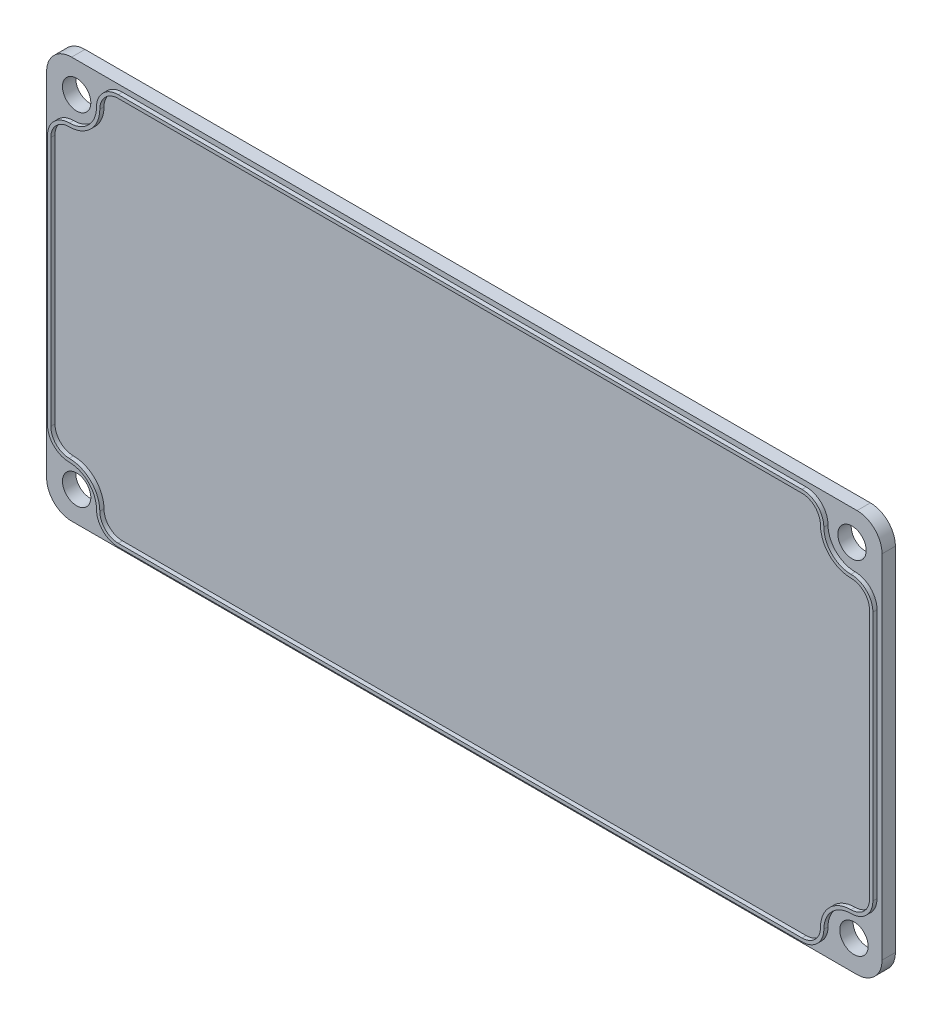
SolidWorks part; units mm, degrees
ref_plane "Plan de face" through (0, 0, 0) normal (0, 0, 1) x (1, 0, 0)
ref_plane "Plan de dessus" through (0, 0, 0) normal (0, 1, 0) x (1, 0, 0)
ref_plane "Plan de droite" through (0, 0, 0) normal (1, 0, 0) x (0, 0, -1)
sketch "Esquisse1" plane through (0, 0, 0) normal (0, 0, 1) x (1, 0, 0)
  line L0 (-50.1, -15) -> (-50.1, 21.1)
  line L1 (-47.1, 24.1) -> (47.1, 24.1)
  line L2 (50.1, 21.1) -> (50.1, -21.1)
  line L3 (47.1, -24.1) -> (-47.1, -24.1)
  line L4 (-50.1, -21.1) -> (-50.1, -15)
  arc A0 (-50.1, 21.1) -> (-47.1, 24.1) centre (-47.1, 21.1) cw
  arc A1 (47.1, 24.1) -> (50.1, 21.1) centre (47.1, 21.1) cw
  arc A2 (50.1, -21.1) -> (47.1, -24.1) centre (47.1, -21.1) cw
  arc A3 (-47.1, -24.1) -> (-50.1, -21.1) centre (-47.1, -21.1) cw
extrude "Boss.-Extru.1" add sketch "Esquisse1" along normal blind 1.6
sketch "Esquisse2" plane through (0, 0, 0) normal (0, 0, 1) x (1, 0, 0)
  line L0 (-41, 22.5) -> (41, 22.5) construction
  line L1 (48.5, 15) -> (48.5, -15) construction
  line L2 (41, -22.5) -> (-41, -22.5) construction
  line L3 (-48.5, -15) -> (-48.5, 15) construction
  line L4 (-49.7, -15) -> (-49.7, 15) construction
  line L5 (-41, 23.7) -> (41, 23.7) construction
  line L6 (49.7, 15) -> (49.7, -15) construction
  line L7 (41, -23.7) -> (-41, -23.7) construction
  line L8 (41, -23.3) -> (-41, -23.3)
  line L9 (-49.3, -15) -> (-49.3, 15)
  line L10 (-41, 23.3) -> (41, 23.3)
  line L11 (49.3, 15) -> (49.3, -15)
  arc A0 (41, 22.5) -> (42.62, 20.88) centre (41, 20.88) cw construction
  arc A1 (42.62, 20.88) -> (46.88, 16.62) centre (46.88, 20.88) ccw construction
  arc A2 (46.88, 16.62) -> (48.5, 15) centre (46.88, 15) cw construction
  arc A3 (48.5, -15) -> (46.88, -16.62) centre (46.88, -15) cw construction
  arc A4 (46.88, -16.62) -> (42.62, -20.88) centre (46.88, -20.88) ccw construction
  arc A5 (42.62, -20.88) -> (41, -22.5) centre (41, -20.88) cw construction
  arc A6 (-41, -22.5) -> (-42.62, -20.88) centre (-41, -20.88) cw construction
  arc A7 (-42.62, -20.88) -> (-46.88, -16.62) centre (-46.88, -20.88) ccw construction
  arc A8 (-46.88, -16.62) -> (-48.5, -15) centre (-46.88, -15) cw construction
  arc A9 (-48.5, 15) -> (-46.88, 16.62) centre (-46.88, 15) cw construction
  arc A10 (-46.88, 16.62) -> (-42.62, 20.88) centre (-46.88, 20.88) ccw construction
  arc A11 (-42.62, 20.88) -> (-41, 22.5) centre (-41, 20.88) cw construction
  arc A12 (-49.7, 15) -> (-46.88, 17.82) centre (-46.88, 15) cw construction
  arc A13 (-46.88, 17.82) -> (-43.82, 20.88) centre (-46.88, 20.88) ccw construction
  arc A14 (-43.82, 20.88) -> (-41, 23.7) centre (-41, 20.88) cw construction
  arc A15 (41, 23.7) -> (43.82, 20.88) centre (41, 20.88) cw construction
  arc A16 (43.82, 20.88) -> (46.88, 17.82) centre (46.88, 20.88) ccw construction
  arc A17 (46.88, 17.82) -> (49.7, 15) centre (46.88, 15) cw construction
  arc A18 (49.7, -15) -> (46.88, -17.82) centre (46.88, -15) cw construction
  arc A19 (46.88, -17.82) -> (43.82, -20.88) centre (46.88, -20.88) ccw construction
  arc A20 (43.82, -20.88) -> (41, -23.7) centre (41, -20.88) cw construction
  arc A21 (-41, -23.7) -> (-43.82, -20.88) centre (-41, -20.88) cw construction
  arc A22 (-43.82, -20.88) -> (-46.88, -17.82) centre (-46.88, -20.88) ccw construction
  arc A23 (-46.88, -17.82) -> (-49.7, -15) centre (-46.88, -15) cw construction
  arc A24 (-41, -23.3) -> (-43.42, -20.88) centre (-41, -20.88) cw
  arc A25 (-43.42, -20.88) -> (-46.88, -17.42) centre (-46.88, -20.88) ccw
  arc A26 (-46.88, -17.42) -> (-49.3, -15) centre (-46.88, -15) cw
  arc A27 (-49.3, 15) -> (-46.88, 17.42) centre (-46.88, 15) cw
  arc A28 (-46.88, 17.42) -> (-43.42, 20.88) centre (-46.88, 20.88) ccw
  arc A29 (-43.42, 20.88) -> (-41, 23.3) centre (-41, 20.88) cw
  arc A30 (41, 23.3) -> (43.42, 20.88) centre (41, 20.88) cw
  arc A31 (43.42, 20.88) -> (46.88, 17.42) centre (46.88, 20.88) ccw
  arc A32 (46.88, 17.42) -> (49.3, 15) centre (46.88, 15) cw
  arc A33 (49.3, -15) -> (46.88, -17.42) centre (46.88, -15) cw
  arc A34 (46.88, -17.42) -> (43.42, -20.88) centre (46.88, -20.88) ccw
  arc A35 (43.42, -20.88) -> (41, -23.3) centre (41, -20.88) cw
  dimension "D1" = 1.2
  dimension "D2" = 0.8
extrude "Extru.-Mince1" add sketch "Esquisse2" along normal blind 2.1 thin thin type mid plane wall 0.4
hole_wizard "Dégagement M31" positions "Esquisse3" profile "Esquisse4" hole size "M3" standard "Ansi Metric" end condition up to next
sketch "Esquisse3" plane through (0, 0, 0) normal (0, 0, -1) x (-1, 0, 0)
  point P0 (-46.5, 20.5)
  point P3 (46.5, 20.5)
  point P6 (46.5, -20.5)
  point P9 (-46.7338, -20.5)
sketch "Esquisse4" plane through (46.5, 20.5, 0) normal (1, 0, 0) x (0, 1, 0)
  line L0 (0, 0) -> (0, 1.6)
  line L1 (0, 1.6) -> (1.7, 1.6)
  line L2 (1.7, 1.6) -> (1.7, 0)
  line L5 (1.7, 0) -> (0, 0)
  line L11 (0, -6.35) -> (0, 107.95) construction
  dimension "Diamètre du perçage jusqu'au prochain" = 3.4
  dimension "Profondeur du perçage jusqu'au prochain" = 1.6
